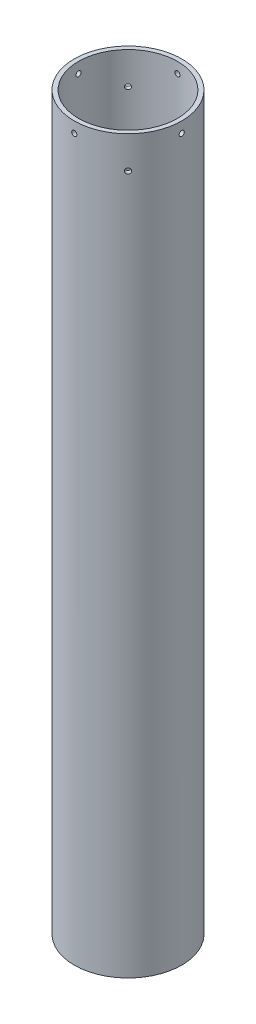
SolidWorks part; units mm, degrees
material "2024 Сплав"
ref_plane "Спереди" through (0, 0, 0) normal (0, 0, 1) x (1, 0, 0)
ref_plane "Сверху" through (0, 0, 0) normal (0, 1, 0) x (1, 0, 0)
ref_plane "Справа" through (0, 0, 0) normal (1, 0, 0) x (0, 0, -1)
sketch "Эскиз1" plane through (0, 0, 0) normal (0, 1, 0) x (1, 0, 0)
  circle A0 centre (0, 0) radius 25
  circle A1 centre (0, 0) radius 23
  dimension "ExDBody" = 50
  dimension "InDBody" = 46
extrude "Бобышка-Вытянуть1" add sketch "Эскиз1" along normal blind 340
sketch "Эскиз2" plane through (0, 0, 0) normal (1, 0, 0) x (0, 0, -1)
  line L0 (23, 340) -> (-23, 340) construction
  circle A0 centre (0, 335) radius 1.2
  dimension "D1" = 5
  dimension "D2" = 2.4
extrude "Вырез-Вытянуть1" cut sketch "Эскиз2" against normal through all
pattern_circular "Круговой массив1" count 4 over 360 about axis through (0, 340, 0) along (0, -1, 0) of "Вырез-Вытянуть1"
ref_plane "Плоскость1" through (0, 0, 0) normal (-0.7071, 0, 0.7071) x (0, -1, 0)
sketch "Эскиз3" plane through (0, 0, 0) normal (-0.7071, 0, 0.7071) x (0, -1, 0)
  line L0 (-340, 0) -> (0, 0) construction
  line L1 (-340, 25) -> (-340, -25) construction
  circle A0 centre (-325, 0) radius 1.2
  dimension "D1" = 2.4
  dimension "D2" = 15
extrude "Вырез-Вытянуть2" cut sketch "Эскиз3" against normal through all
pattern_circular "Круговой массив2" count 4 over 360 about axis through (0, 340, 0) along (0, -1, 0) of "Вырез-Вытянуть2"
